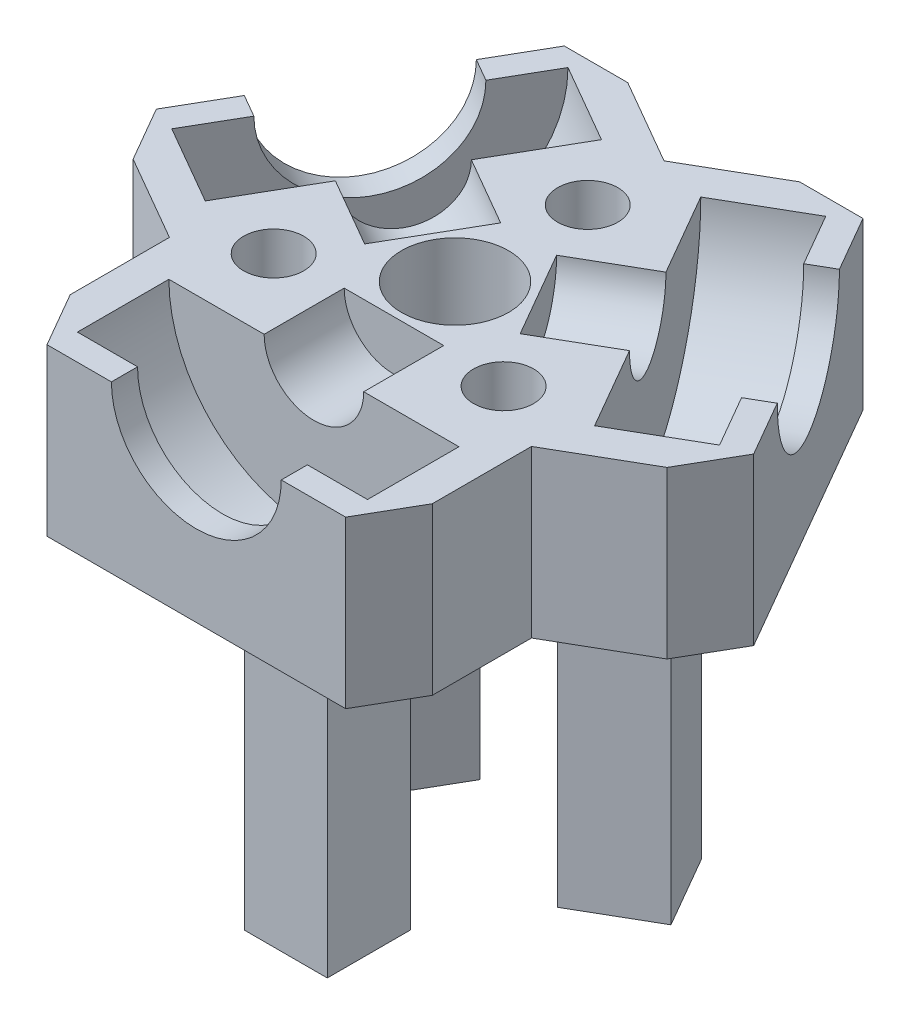
SolidWorks part; units mm, degrees
ref_plane "Front Plane" through (0, 0, 0) normal (0, 0, 1) x (1, 0, 0)
ref_plane "Top Plane" through (0, 0, 0) normal (0, 1, 0) x (1, 0, 0)
ref_plane "Right Plane" through (0, 0, 0) normal (1, 0, 0) x (0, 0, -1)
sketch "Sketch1" plane through (0, 0, 0) normal (0, 1, 0) x (1, 0, 0)
  line L1 (11.43, -19.7973) -> (22.86, 0)
  line L2 (22.86, 0) -> (11.43, 19.7973)
  line L3 (11.43, 19.7973) -> (-11.43, 19.7973)
  line L4 (-11.43, 19.7973) -> (-22.86, 0)
  line L5 (-22.86, 0) -> (-11.43, -19.7973)
  line L6 (-11.43, -19.7973) -> (11.43, -19.7973)
  circle A0 centre (0, 0) radius 19.7973 construction
  dimension "D1" = 22.86
extrude "Boss-Extrude1" add sketch "Sketch1" along normal blind 12.7 contours L4 L5 L6 L1 L2 L3
sketch "Sketch2" plane through (0, 0, 0) normal (0, -1, 0) x (1, 0, 0)
  circle A0 centre (0, 0) radius 4.1
  circle A1 centre (0, 0) radius 7.1
  dimension "D1" = 8.2
  dimension "D2" = 3
extrude "Boss-Extrude2" add sketch "Sketch2" along normal blind 3.5
sketch "Sketch4" plane through (0, 0, 0) normal (0, -1, 0) x (1, 0, 0)
  line L0 (12.8025, -3.7254) -> (7.3033, -0.5504)
  line L1 (-3.175, 12.95) -> (3.175, 12.95)
  line L2 (-3.175, 12.95) -> (-3.175, 6.6)
  line L3 (-3.175, 6.6) -> (3.175, 6.6)
  line L4 (3.175, 12.95) -> (3.175, 6.6)
  line L5 (-3.175, 12.95) -> (3.175, 6.6) construction
  line L6 (-3.175, 6.6) -> (3.175, 12.95) construction
  line L7 (12.8025, -3.7254) -> (9.6275, -9.2246)
  line L8 (9.6275, -9.2246) -> (4.1283, -6.0496)
  line L9 (7.3033, -0.5504) -> (4.1283, -6.0496)
  line L10 (-9.6275, -9.2246) -> (-4.1283, -6.0496)
  line L11 (-9.6275, -9.2246) -> (-12.8025, -3.7254)
  line L12 (-12.8025, -3.7254) -> (-7.3033, -0.5504)
  line L13 (-4.1283, -6.0496) -> (-7.3033, -0.5504)
  circle A1 centre (0, 0) radius 4.1 construction
  circle A2 centre (0, 0) radius 4.1 construction
  point P0 (0, 9.775)
  point P18 (0, 0)
  dimension "D1" = 6.35
  dimension "D2" = 2.5
  dimension "D4" = 2.5
  dimension "D5" = 2.5
  dimension "D3" = 3
extrude "Boss-Extrude4" add sketch "Sketch4" along normal blind 25.4
sketch "Sketch5" plane through (0, 12.7, 0) normal (0, 1, 0) x (1, 0, 0)
  line L14 (0, -19.7973) -> (0, -4.6723)
  line L15 (-11.43, -19.7973) -> (11.43, -19.7973) construction
  line L16 (0, -4.6723) -> (-3.81, -4.6723)
  line L17 (-3.81, -4.6723) -> (-3.81, -10.7973)
  line L18 (-3.81, -10.7973) -> (-11.1, -10.7973)
  line L19 (-11.1, -10.7973) -> (-11.1, -17.7973)
  line L20 (-11.1, -17.7973) -> (-6.5, -17.7973)
  line L21 (-6.5, -17.7973) -> (-6.5, -19.7973)
  line L22 (-6.5, -19.7973) -> (0, -19.7973)
  dimension "D1" = 6.5
  dimension "D2" = 11.1
  dimension "D3" = 2
  dimension "D4" = 7
  dimension "D5" = 6.125
  dimension "D6" = 3.81
revolve "Cut-Revolve1" cut sketch "Sketch5" angle 360 about L14
pattern_circular "CirPattern1" count 3 over 360 about axis through (0, -3.5, 0) along (0, 1, 0) of "Cut-Revolve1" reverse direction yes
sketch "Sketch6" plane through (0, 12.7, 0) normal (0, 1, 0) x (1, 0, 0)
  circle A0 centre (0, 0) radius 4.1
  dimension "D1" = 8.2
extrude "Cut-Extrude1" cut sketch "Sketch6" against normal through all
sketch "Sketch7" plane through (0, 12.7, 0) normal (0, 1, 0) x (1, 0, 0)
  circle A0 centre (0, 10.16) radius 2.3
  circle A1 centre (8.7988, -5.08) radius 2.3
  circle A2 centre (-8.7988, -5.08) radius 2.3
  circle A3 centre (0, 0) radius 10.16 construction
  point P2 (0, 12.7912)
  point P3 (-1.7413, -0.4085)
  point P11 (0, 0)
  dimension "D1" = 4.6
  dimension "D2" = 20.32
  dimension "D3" = 3
extrude "Cut-Extrude2" cut sketch "Sketch7" against normal blind 5.7
sketch "Sketch8" plane through (0, 0, 0) normal (0, -1, 0) x (1, 0, 0)
  line L0 (-22.86, 0) -> (-7.0264, 4.0567)
  line L1 (-7.0264, 4.0567) -> (-11.43, 19.7973)
  line L2 (-11.43, 19.7973) -> (-22.86, 0)
  line L3 (11.43, 19.7973) -> (7.0264, 4.0567)
  line L4 (7.0264, 4.0567) -> (22.86, 0)
  line L5 (22.86, 0) -> (11.43, 19.7973)
  line L6 (11.43, -19.7973) -> (0, -8.1133)
  line L7 (0, -8.1133) -> (-11.43, -19.7973)
  line L8 (-11.43, -19.7973) -> (11.43, -19.7973)
  line L9 (22.86, 0) -> (11.43, -19.7973) construction
  point P3 (13.4132, -16.3623)
  point P13 (0, 0)
  point P15 (0, 0)
  dimension "D1" = 11.684
  dimension "D2" = 3
extrude "Cut-Extrude3" [suppressed] cut sketch "Sketch8" against normal blind 4.572
sketch "Sketch9" plane through (0, 12.7, 0) normal (0, 1, 0) x (1, 0, 0)
  line L0 (-6.5772, 19.7973) -> (0, 16)
  line L1 (11.43, 19.7973) -> (-11.43, 19.7973) construction
  line L2 (20.4336, -4.2027) -> (13.8564, -8)
  line L3 (0, 16) -> (6.5772, 19.7973)
  line L4 (13.8564, -8) -> (13.8564, -15.5947)
  line L5 (6.5772, 19.7973) -> (-6.5772, 19.7973)
  line L6 (13.8564, -15.5947) -> (20.4336, -4.2027)
  line L7 (-13.8564, -15.5947) -> (-13.8564, -8)
  line L8 (-13.8564, -8) -> (-20.4336, -4.2027)
  line L9 (-20.4336, -4.2027) -> (-13.8564, -15.5947)
  point P6 (0, 19.7973)
  point P7 (0, 19.7973)
  point P15 (0, 0)
  point P16 (0, 0)
  dimension "D1" = 3.7973
  dimension "D2" = 13.1544
  dimension "D3" = 3
extrude "Cut-Extrude4" cut sketch "Sketch9" against normal through all
